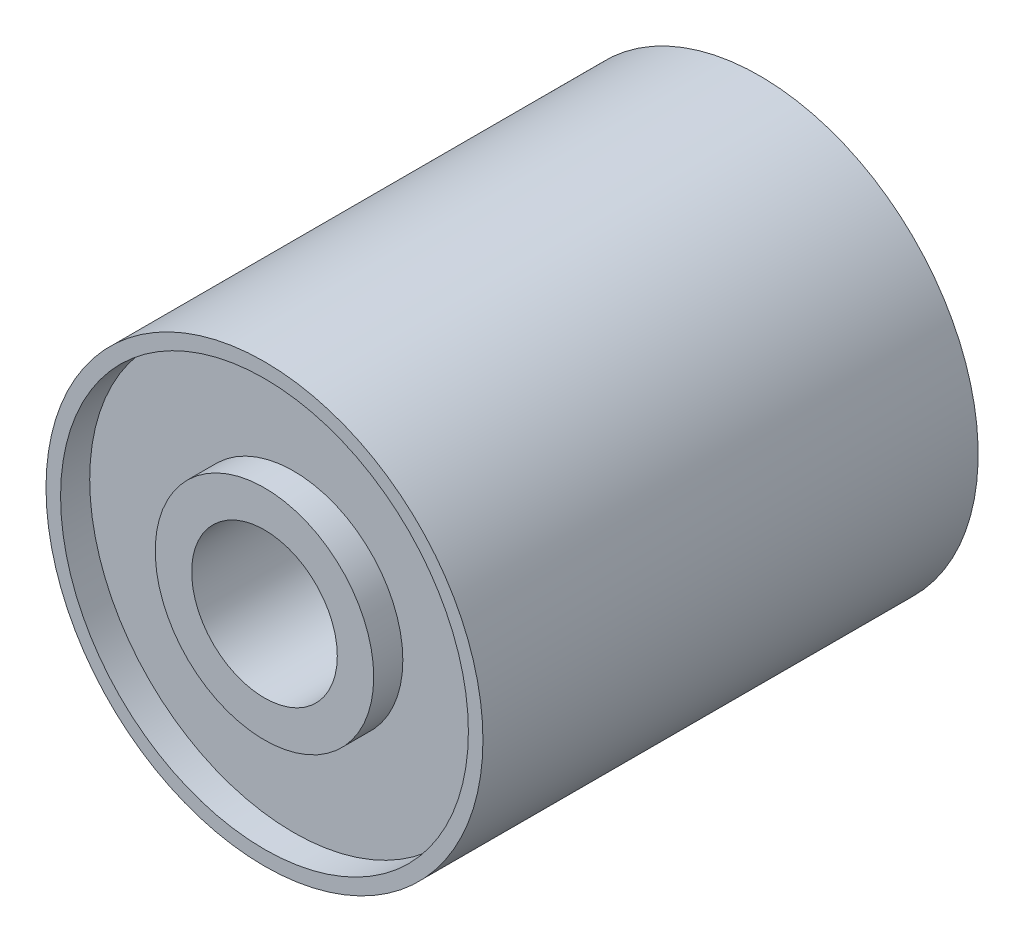
SolidWorks part; units mm, degrees
material "1023 碳钢板 (SS)"
ref_plane "前视基准面" through (0, 0, 0) normal (0, 0, 1) x (1, 0, 0)
ref_plane "上视基准面" through (0, 0, 0) normal (0, 1, 0) x (1, 0, 0)
ref_plane "右视基准面" through (0, 0, 0) normal (1, 0, 0) x (0, 0, -1)
sketch "草图1" plane through (0, 0, 0) normal (0, 0, 1) x (1, 0, 0)
  circle A0 centre (0, 0) radius 1.5
  dimension "D1" = 3
extrude "凸台-拉伸1" add sketch "草图1" along normal blind 3
sketch "草图2" plane through (0, 0, 3) normal (0, 0, 1) x (1, 0, 0)
  circle A0 centre (0, 0) radius 1.4
  circle A1 centre (0, 0) radius 1.5 construction
  circle A2 centre (0, 0) radius 1.5
  dimension "D1" = 0.1
extrude "凸台-拉伸2" add sketch "草图2" along normal blind 0.2
sketch "草图3" plane through (0, 0, 0) normal (0, 0, -1) x (-1, 0, 0)
  circle A0 centre (0, 0) radius 1.4
  circle A1 centre (0, 0) radius 1.5 construction
  circle A2 centre (0, 0) radius 1.5
  dimension "D1" = 0.1
extrude "凸台-拉伸3" add sketch "草图3" along normal blind 0.2
sketch "草图4" plane through (0, 0, 0) normal (0, 0, -1) x (-1, 0, 0)
  circle A0 centre (0, 0) radius 0.75
  circle A1 centre (0, 0) radius 0.5
  dimension "D1" = 1.5
  dimension "D2" = 1
extrude "凸台-拉伸4" add sketch "草图4" along normal blind 0.2
sketch "草图5" plane through (0, 0, 3) normal (0, 0, 1) x (1, 0, 0)
  circle A0 centre (0, 0) radius 0.75
  circle A1 centre (0, 0) radius 0.5
  dimension "D1" = 1.5
  dimension "D2" = 1
extrude "凸台-拉伸5" add sketch "草图5" along normal blind 0.2
sketch "草图7" plane through (0, 0, 0) normal (0, 0, -1) x (-1, 0, 0)
  circle A1 centre (0, 0) radius 0.5
  circle A2 centre (0, 0) radius 0.5
  dimension "D1" = 0
extrude "切除-拉伸2" cut sketch "草图7" against normal through all
